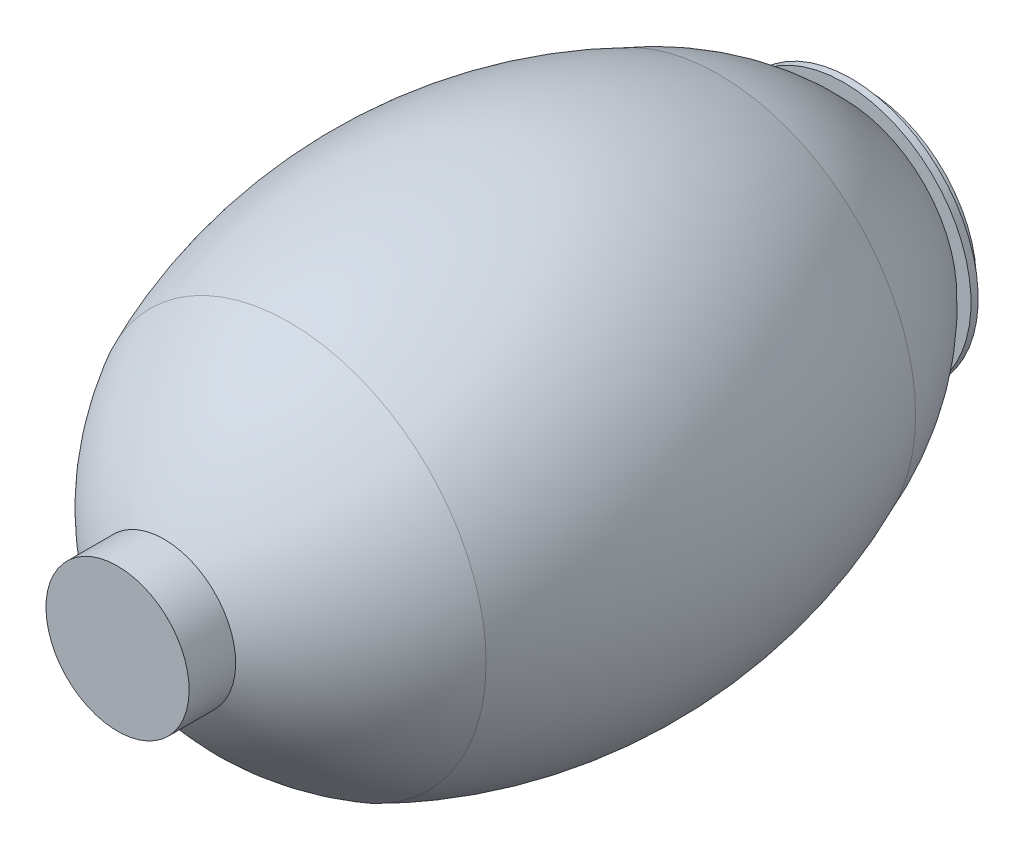
SolidWorks part; units mm, degrees
ref_plane "Front Plane" through (0, 0, 0) normal (0, 0, 1) x (1, 0, 0)
ref_plane "Top Plane" through (0, 0, 0) normal (0, 1, 0) x (1, 0, 0)
ref_plane "Right Plane" through (0, 0, 0) normal (1, 0, 0) x (0, 0, -1)
sketch "Sketch1" plane through (0, 0, 0) normal (1, 0, 0) x (0, 0, -1)
  line L0 (0, 0) -> (0, 20)
  line L1 (0, 20) -> (13, 20)
  line L2 (203, 31.5) -> (203, 35.5)
  line L3 (203, 35.5) -> (205, 35.5)
  line L4 (205, 35.5) -> (205, 31)
  line L5 (205, 31) -> (209, 31)
  line L6 (209, 31) -> (209, 0)
  line L7 (209, 0) -> (0, 0)
  line L8 (108, 67.5) -> (176.7271, 67.5) construction
  line L9 (108, 67.5) -> (108, 0) construction
  arc A0 (13, 20) -> (48, 55) centre (91.6862, -23.6862) cw
  arc A1 (48, 55) -> (168, 55) centre (108, -82.75) cw
  arc A2 (168, 55) -> (203, 31.5) centre (136.7263, -29.3917) cw
  dimension "D1" = 67.5
  dimension "D13" = 90
  dimension "D14" = 90
  dimension "D2" = 55
  dimension "D3" = 120
  dimension "D4" = 13
  dimension "D5" = 31.5
  dimension "D6" = 20
  dimension "D7" = 35
  dimension "D8" = 35
  dimension "D9" = 35.5
  dimension "D10" = 2
  dimension "D11" = 4
  dimension "D12" = 31
revolve "Revolve1" add sketch "Sketch1" angle 360 about L7 region at (0, 28.4675, -108.538)
